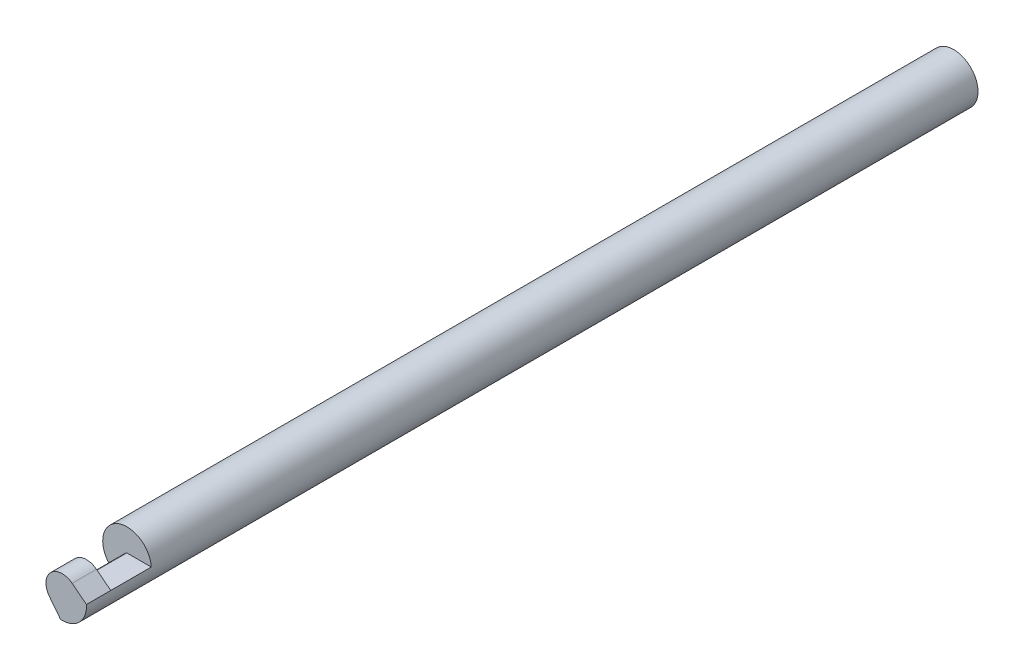
SolidWorks part; units mm, degrees
material "AISI 316 Annealed Stainless Steel Bar (SS)"
ref_plane "Front" through (0, 0, 0) normal (0, 0, 1) x (1, 0, 0)
ref_plane "Top" through (0, 0, 0) normal (0, 1, 0) x (1, 0, 0)
ref_plane "Right" through (0, 0, 0) normal (1, 0, 0) x (0, 0, -1)
ref_axis "X" through (-80.9, 0, 0) along (1, 0, 0)
ref_axis "Y" through (0, -50, 0) along (0, 1, 0)
ref_axis "Z" through (0, 0, -80.9) along (0, 0, 1)
sketch "Sketch1" plane through (0, 0, 0) normal (1, 0, 0) x (0, 0, -1)
  line L0 (0, 0) -> (0, 1.5)
  line L1 (0, 1.5) -> (55, 1.5)
  line L2 (55, 1.5) -> (55, 0)
  line L3 (55, 0) -> (0, 0)
  line L4 (-9.841, 0) -> (-3.2015, 0) construction
  dimension "D1" = 3
  dimension "D2" = 55
revolve "Revolve1" add sketch "Sketch1" angle 360 about L4
sketch "Sketch2" plane through (0, 0, 0) normal (0, 0, 1) x (1, 0, 0)
  line L0 (0, 0.1) -> (1.4967, 0.1)
  line L1 (-0.1, 0) -> (-0.1, -1.4967)
  arc A0 (0, 0.1) -> (-0.1, 0) centre (0, 0) ccw
  circle A2 centre (0, 0) radius 1.5
  arc A3 (1.4967, 0.1) -> (-0.1, -1.4967) centre (0, 0) ccw
  dimension "D2" = 0.1
  dimension "D1" = 0
extrude "Cut-Extrude1" cut sketch "Sketch2" against normal blind 2.5 from offset 1.5 offset against normal yes
sketch "Sketch3" plane through (0, 0, 0) normal (0, 0, 1) x (1, 0, 0)
  line L0 (1.4967, 0.1) -> (0.6155, 0.7881)
  line L1 (-0.1, -1.4967) -> (-0.7881, -0.6155)
  arc A0 (0.6155, 0.7881) -> (-0.7881, -0.6155) centre (0, 0) ccw
  circle A2 centre (0, 0) radius 1.5 construction
  arc A3 (1.4967, 0.1) -> (-0.1, -1.4967) centre (0, 0) ccw
  dimension "D1" = 1
extrude "Cut-Extrude2" cut sketch "Sketch3" against normal up to surface (1.5 mm away) up to face at (-0.1208, 0.1208, -1.5)
